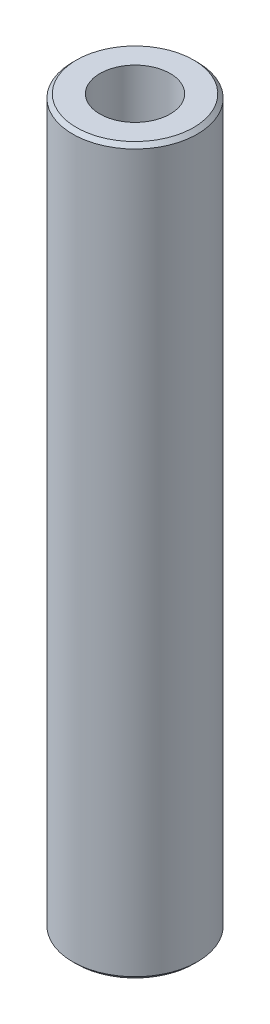
SolidWorks part; units mm, degrees
ref_plane "Front Plane" through (0, 0, 0) normal (0, 0, 1) x (1, 0, 0)
ref_plane "Top Plane" through (0, 0, 0) normal (0, 1, 0) x (1, 0, 0)
ref_plane "Right Plane" through (0, 0, 0) normal (1, 0, 0) x (0, 0, -1)
sketch "Sketch1" plane through (0, 0, 0) normal (0, 1, 0) x (1, 0, 0)
  circle A0 centre (0, 0) radius 45
  dimension "SHAFT_OD" = 90
extrude "Boss-Extrude1" add sketch "Sketch1" along normal blind 522.837
sketch "Sketch2" plane through (0, 0, 0) normal (0, 1, 0) x (1, 0, 0)
  circle A0 centre (0, 0) radius 25.3595
  dimension "BORE_D" = 50.719
extrude "Cut-Extrude1" cut sketch "Sketch2" along normal through all
chamfer "Chamfer1" distance 2.7414 angle 45 2 edges at (0, 522.837, 45) (0, 0, 45)
